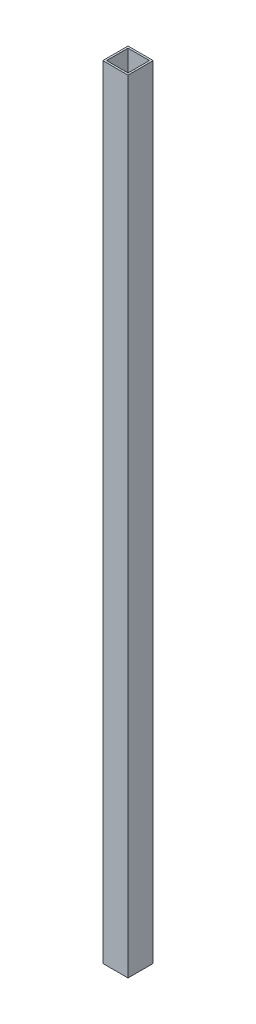
SolidWorks part; units mm, degrees
ref_plane "Front" through (0, 0, 0) normal (0, 0, 1) x (1, 0, 0)
ref_plane "Top" through (0, 0, 0) normal (0, 1, 0) x (1, 0, 0)
ref_plane "Right" through (0, 0, 0) normal (1, 0, 0) x (0, 0, -1)
sketch "Sketch1" plane through (0, 0, 0) normal (0, 1, 0) x (1, 0, 0)
  line L1 (20, -20) -> (-20, -20)
  line L2 (20, -20) -> (20, 20)
  line L3 (20, 20) -> (-20, 20)
  line L4 (-20, -20) -> (-20, 20)
  line L5 (20, -20) -> (-20, 20) construction
  line L6 (20, 20) -> (-20, -20) construction
  point P0 (0, 0)
  dimension "D1" = 40
  dimension "D2" = 40
extrude "Boss-Extrude1" add sketch "Sketch1" along normal blind 1240
sketch "Sketch2" plane through (0, 1240, 0) normal (0, 1, 0) x (1, 0, 0)
  line L1 (17, -17) -> (-17, -17)
  line L2 (17, -17) -> (17, 17)
  line L3 (17, 17) -> (-17, 17)
  line L4 (-17, -17) -> (-17, 17)
  line L5 (17, -17) -> (-17, 17) construction
  line L6 (17, 17) -> (-17, -17) construction
  point P0 (0, 0)
  dimension "D1" = 34
  dimension "D2" = 34
extrude "Cut-Extrude1" cut sketch "Sketch2" against normal through all
